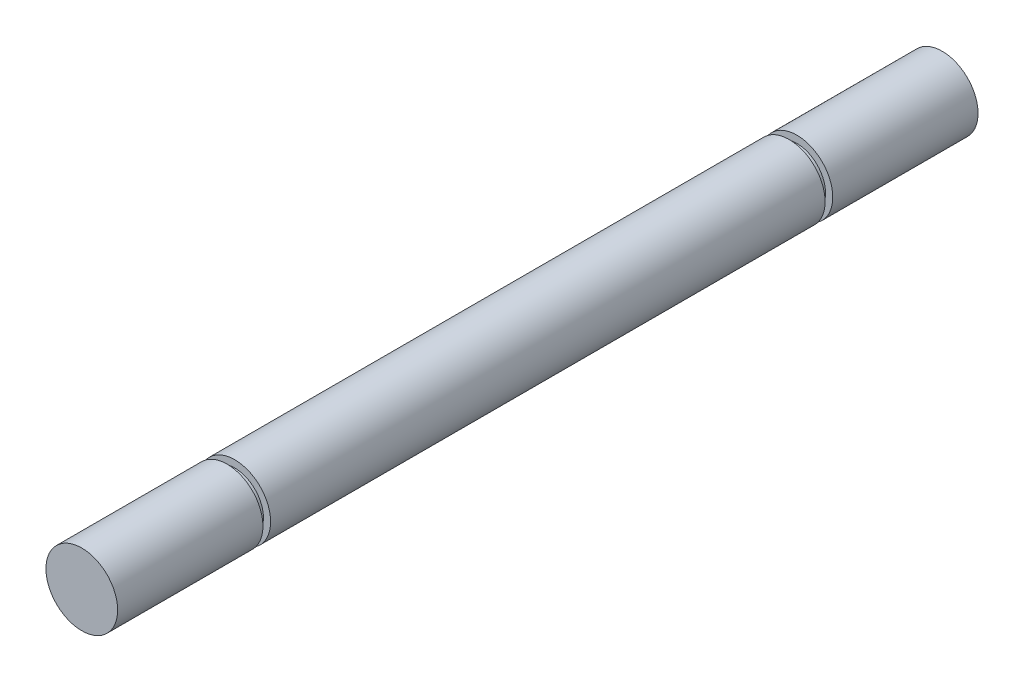
SolidWorks part; units mm, degrees
ref_plane "Front Plane" through (0, 0, 0) normal (0, 0, 1) x (1, 0, 0)
ref_plane "Top Plane" through (0, 0, 0) normal (0, 1, 0) x (1, 0, 0)
ref_plane "Right Plane" through (0, 0, 0) normal (1, 0, 0) x (0, 0, -1)
sketch "Sketch1" plane through (0, 0, 0) normal (0, 0, 1) x (1, 0, 0)
  circle A0 centre (0, 0) radius 4.7625
  dimension "D1" = 9.525
extrude "Boss-Extrude1" add sketch "Sketch1" along normal blind 73.66
sketch "Sketch2" plane through (0, 0, 0) normal (0, 0, -1) x (-1, 0, 0)
  circle A0 centre (0, 0) radius 3.81
  dimension "D1" = 7.62
extrude "Boss-Extrude2" add sketch "Sketch2" along normal blind 1.016
sketch "Sketch3" plane through (0, 0, -1.016) normal (0, 0, -1) x (-1, 0, 0)
  circle A0 centre (0, 0) radius 4.7625
  dimension "D1" = 9.525
extrude "Boss-Extrude3" add sketch "Sketch3" along normal blind 19.304
sketch "Sketch4" plane through (0, 0, 73.66) normal (0, 0, 1) x (1, 0, 0)
  circle A0 centre (0, 0) radius 3.81
  dimension "D1" = 7.62
extrude "Boss-Extrude4" add sketch "Sketch4" along normal blind 1.016
sketch "Sketch5" plane through (0, 0, 74.676) normal (0, 0, 1) x (1, 0, 0)
  circle A0 centre (0, 0) radius 4.7625
  dimension "D1" = 9.525
extrude "Boss-Extrude5" add sketch "Sketch5" along normal blind 19.304
